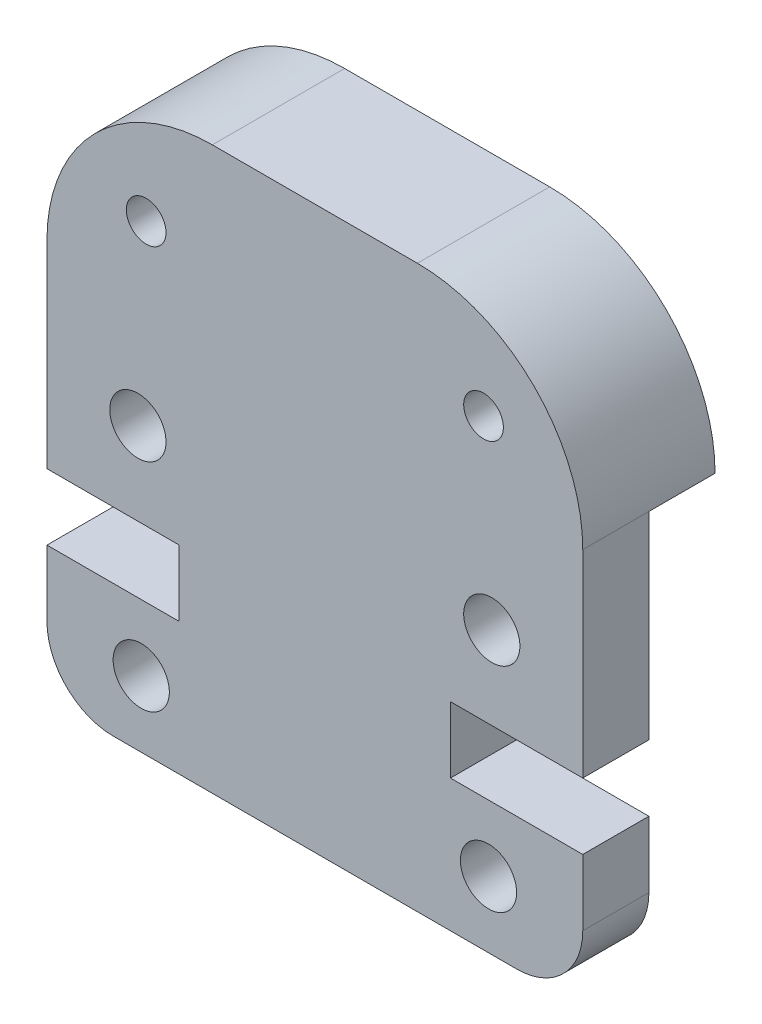
SolidWorks part; units mm, degrees
ref_plane "Front Plane" through (0, 0, 0) normal (0, 0, 1) x (1, 0, 0)
ref_plane "Top Plane" through (0, 0, 0) normal (0, 1, 0) x (1, 0, 0)
ref_plane "Right Plane" through (0, 0, 0) normal (1, 0, 0) x (0, 0, -1)
sketch "Sketch1" plane through (0, 0, 0) normal (0, 0, 1) x (1, 0, 0)
  line L0 (0, 16.98) -> (0, 0) construction
  line L1 (3.1, 16.98) -> (-3.1, 16.98)
  line L2 (6.1, 0) -> (-6.1, 0)
  line L3 (-8.1, 6) -> (-4.1, 6)
  line L4 (-4.1, 6) -> (-4.1, 4)
  line L5 (-4.1, 4) -> (-8.1, 4)
  line L6 (-8.1, 2) -> (-8.1, 4)
  line L7 (8.1, 11.98) -> (8.1, 6)
  line L8 (-8.1, 11.98) -> (-8.1, 6)
  line L24 (8.1, 2) -> (8.1, 4)
  line L27 (4.1, 4) -> (8.1, 4)
  line L30 (4.1, 6) -> (4.1, 4)
  line L31 (8.1, 6) -> (4.1, 6)
  circle A0 centre (-5.25, 2) radius 0.85
  circle A1 centre (-5.1, 13.98) radius 0.6
  arc A2 (-8.1, 11.98) -> (-3.1, 16.98) centre (-3.1, 11.98) cw
  arc A3 (-6.1, 0) -> (-8.1, 2) centre (-6.1, 2) cw
  circle A4 centre (-5.35, 8.5) radius 0.85
  circle A10 centre (5.35, 8.5) radius 0.85
  arc A12 (6.1, 0) -> (8.1, 2) centre (6.1, 2) ccw
  arc A14 (8.1, 11.98) -> (3.1, 16.98) centre (3.1, 11.98) ccw
  circle A16 centre (5.1, 13.98) radius 0.6
  circle A18 centre (5.25, 2) radius 0.85
  dimension "D1" = 1.7
  dimension "D2" = 1.2
  dimension "D5" = 5
  dimension "D6" = 6.1
  dimension "D4" = 2
  dimension "D3" = 16.98
  dimension "D7" = 3
  dimension "D10" = 8.5
  dimension "D9" = 2.75
  dimension "D8" = 3
extrude "Boss-Extrude1" add sketch "Sketch1" along normal blind 4
sketch "Sketch2" plane through (0, 0, 0) normal (0, 0, 1) x (1, 0, 0)
  line L0 (-8.1, 0) -> (8.1, 0)
  line L1 (8.1, 0) -> (8.1, 11.98)
  line L2 (8.1, 11.98) -> (-8.1, 11.98)
  line L3 (-8.1, 11.98) -> (-8.1, 0)
extrude "Cut-Extrude1" cut sketch "Sketch2" along normal blind 2
equation "\"D6@Sketch1\"= ( \"fingerWidth@parametersSketch@prostheticParameters.SLDPRT\" - 4 ) / 2'Finger Width - Radius"
equation "\"D3@Sketch1\"= ( \"HL@parametersSketch@prostheticParameters.SLDPRT\" * 0.108 ) - 3 'DIP Legth-Sil. Sh. DIP"
equation "\"D1@Sketch1\"= 1.5 + \"tol1@parametersSketch@prostheticParameters.SLDPRT\""
equation "\"D2@Sketch1\"= 1 + \"tol1@parametersSketch@prostheticParameters.SLDPRT\""
